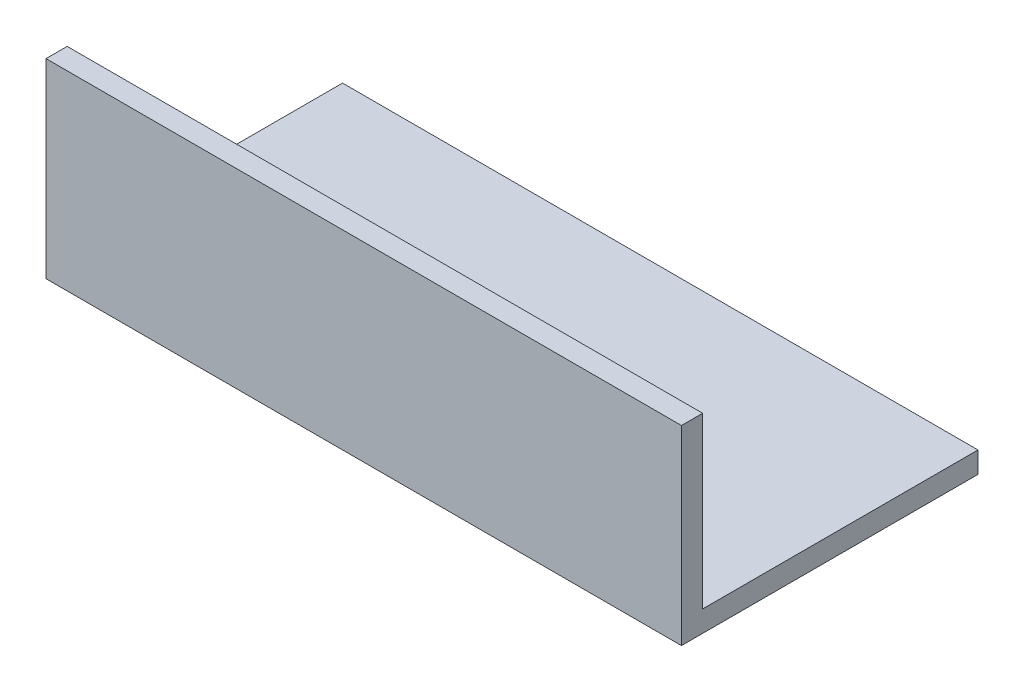
SolidWorks part; units mm, degrees
ref_plane "正面" through (0, 0, 0) normal (0, 0, 1) x (1, 0, 0)
ref_plane "平面" through (0, 0, 0) normal (0, 1, 0) x (1, 0, 0)
ref_plane "右側面" through (0, 0, 0) normal (1, 0, 0) x (0, 0, -1)
sketch "ｽｹｯﾁ1" plane through (0, 0, 0) normal (0, 0, 1) x (1, 0, 0)
  line L1 (-75, 20) -> (75, 20)
  line L2 (-75, 20) -> (-75, -20)
  line L3 (-75, -20) -> (75, -20)
  line L4 (75, 20) -> (75, -20)
  line L5 (-75, 20) -> (75, -20) construction
  line L6 (-75, -20) -> (75, 20) construction
  point P0 (0, 0)
  dimension "D1" = 40
  dimension "D2" = 150
extrude "ﾎﾞｽ - 押し出し1" add sketch "ｽｹｯﾁ1" along normal blind 5
sketch "ｽｹｯﾁ3" plane through (0, -20, 0) normal (0, -1, 0) x (1, 0, 0)
  line L0 (75, 5) -> (75, 0) construction
  line L1 (-75, 5) -> (75, 5)
  line L2 (-75, 5) -> (-75, -65)
  line L3 (-75, -65) -> (75, -65)
  line L4 (75, 5) -> (75, -65)
  dimension "D1" = 70
extrude "ﾎﾞｽ - 押し出し2" add sketch "ｽｹｯﾁ3" along normal blind 5
